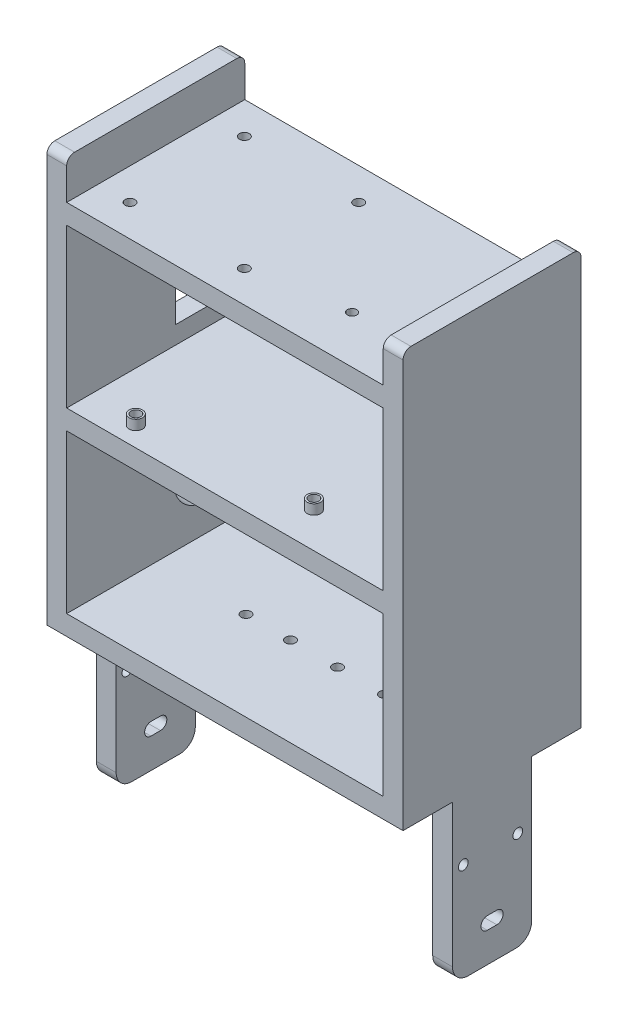
SolidWorks part; units mm, degrees
ref_plane "Front Plane" through (0, 0, 0) normal (0, 0, 1) x (1, 0, 0)
ref_plane "Top Plane" through (0, 0, 0) normal (0, 1, 0) x (1, 0, 0)
ref_plane "Right Plane" through (0, 0, 0) normal (1, 0, 0) x (0, 0, -1)
sketch "Sketch1" plane through (0, 0, 0) normal (0, 0, 1) x (1, 0, 0)
  line L0 (0, 0) -> (101.6, 0)
  line L1 (101.6, 0) -> (101.6, 127)
  line L2 (0, 0) -> (0, 127)
  line L3 (0, 57.15) -> (101.6, 57.15)
  line L4 (101.6, 57.15) -> (101.6, 50.8)
  line L5 (101.6, 50.8) -> (0, 50.8)
  line L6 (0, 50.8) -> (0, 57.15)
  line L7 (0, 114.3) -> (101.6, 114.3)
  line L8 (101.6, 114.3) -> (101.6, 107.95)
  line L9 (101.6, 107.95) -> (0, 107.95)
  line L10 (0, 107.95) -> (0, 114.3)
  line L11 (-6.35, 0) -> (-6.35, -6.35)
  line L12 (0, -6.35) -> (101.6, -6.35)
  line L13 (107.95, 0) -> (107.95, -6.35)
  line L14 (101.6, 127) -> (107.95, 127)
  line L15 (107.95, 127) -> (107.95, 0)
  line L16 (107.95, 0) -> (101.6, 0)
  line L17 (0, 127) -> (-6.35, 127)
  line L18 (-6.35, 127) -> (-6.35, 0)
  line L19 (-6.35, 0) -> (0, 0)
  line L20 (-6.35, -6.35) -> (0, -6.35)
  line L21 (107.95, -6.35) -> (101.6, -6.35)
  dimension "D1" = 101.6
  dimension "D2" = 127
  dimension "D3" = 57.15
  dimension "D4" = 6.35
  dimension "D5" = 114.3
  dimension "D6" = 6.35
  dimension "D7" = 6.35
  dimension "D8" = 6.35
  dimension "D9" = 6.35
extrude "Boss-Extrude1" add sketch "Sketch1" against normal blind 57.15 contours L16 L15 L14 L1 | L18 L19 L2 L17 | L9 L1 L7 L2 | L5 L1 L3 L2 | L21 L13 L16 L0 L19 L11 L20 L12 region at (-3.175, 63.5, 0) region at (50.8, -3.175, 0) region at (104.775, 63.5, 0) region at (50.8, 53.975, 0) region at (50.8, 111.125, 0)
sketch "Sketch2" plane through (107.95, 0, 0) normal (1, 0, 0) x (0, 0, -1)
  line L0 (28.575, -6.35) -> (28.575, 127) construction
  line L1 (57.15, -6.35) -> (0, -6.35) construction
  line L2 (57.15, 127) -> (0, 127) construction
  line L3 (41.275, -6.35) -> (41.275, -57.15)
  line L4 (15.875, -6.35) -> (15.875, -57.15)
  line L5 (15.875, -6.35) -> (41.275, -6.35)
  line L6 (15.875, -57.15) -> (41.275, -57.15)
  dimension "D1" = 12.7
  dimension "D2" = 50.8
extrude "Boss-Extrude2" add sketch "Sketch2" against normal blind 6.35
ref_plane "Plane1" through (50.8, 0, 0) normal (1, 0, 0) x (0, 0, -1)
mirror "Mirror1" about plane through (50.8, 0, 0) normal (1, 0, 0) of "Boss-Extrude2"
sketch "Sketch4" plane through (-6.35, 0, 0) normal (-1, 0, 0) x (0, 0, 1)
  line L0 (-30.1047, 127) -> (-28.575, -55.7505) construction
  line L1 (-57.15, 127) -> (0, 127) construction
  text T0 "<r90>LEEK</r></r>" font "Arial" height in points 36
extrude "Boss-Extrude3" add sketch "Sketch4" along normal blind 0.508
sketch "Sketch5" plane through (107.95, 0, 0) normal (1, 0, 0) x (0, 0, -1)
  line L0 (28.575, -55.7505) -> (28.575, -5.8921) construction
  line L1 (27.051, -45.527) -> (30.099, -45.527) construction
  line L2 (27.051, -43.495) -> (30.099, -43.495)
  line L3 (27.051, -47.559) -> (30.099, -47.559)
  line L5 (15.875, -57.15) -> (41.275, -57.15) construction
  arc A1 (27.051, -43.495) -> (27.051, -47.559) centre (27.051, -45.527) ccw
  arc A2 (30.099, -47.559) -> (30.099, -43.495) centre (30.099, -45.527) ccw
  point P8 (28.575, -45.527)
  dimension "D3" = 9.591
  dimension "D1" = 1.524
  dimension "D2" = 4.064
extrude "Cut-Extrude1" cut sketch "Sketch5" against normal through all
sketch "Sketch7" plane through (-6.35, 0, 0) normal (-1, 0, 0) x (0, 0, 1)
  circle A0 centre (-36.8351, -25.527) radius 1.5748
  circle A1 centre (-19.3345, -25.527) radius 1.5748
  arc A2 (-30.099, -43.495) -> (-30.099, -47.559) centre (-30.099, -45.527) ccw construction
  point P12 (-32.131, -45.527)
  dimension "D1" = 3.1496
  dimension "D2" = 17.5006
  dimension "D3" = 6.7361
  dimension "D4" = 20
fillet "Fillet1" radius 5.0013 4 edges at (-3.175, -57.15, -15.875) (-3.175, -57.15, -41.275) (104.775, -57.15, -41.275) (104.775, -57.15, -15.875)
extrude "Cut-Extrude2" cut sketch "Sketch7" against normal through all
sketch "Sketch8" plane through (-6.35, 0, 0) normal (-1, 0, 0) x (0, 0, 1)
  line L0 (-57.15, 127) -> (-57.15, -6.35) construction
  line L1 (-56.007, 21.2712) -> (-32.893, 21.2712)
  line L2 (-32.893, 21.2712) -> (-32.893, 16.8288)
  line L3 (-32.893, 16.8288) -> (-56.007, 16.8288)
  line L4 (-56.007, 16.8288) -> (-56.007, 21.2712)
  line L5 (-56.007, 19.05) -> (-32.893, 19.05) construction
  line L6 (-44.45, 30.607) -> (-44.45, 7.493) construction
  line L7 (-57.15, -6.35) -> (-41.275, -6.35) construction
  circle A0 centre (-44.45, 19.05) radius 10.033
  circle A1 centre (-44.45, 19.05) radius 11.557
  dimension "D1" = 12.7
  dimension "D2" = 20.066
  dimension "D3" = 23.114
  dimension "D6" = 25.4
  dimension "D4" = 23.114
  dimension "D5" = 4.4425
extrude "Cut-Extrude3" cut sketch "Sketch8" against normal up to surface (6.35 mm away) contours L1 A0 | L1 A0 L3 | L3 A0 region at (-6.35, 24.5313, -44.45) region at (-6.35, 19.05, -44.45) region at (-6.35, 13.5687, -44.45) up to face at (0, 25.4, -28.575)
extrude "Boss-Extrude6" add sketch "Sketch8<3>" along normal blind 3.81 contours L1 A1 A0 | L3 A1 A0 region at (-6.35, 30.3617, -44.45) region at (-6.35, 16.5835, -55.0128)
sketch "Sketch8<3>" plane through (-6.35, 0, 0) normal (-1, 0, 0) x (0, 0, 1) same geometry as "Sketch8"
sketch "Sketch10" plane through (0, 57.15, 0) normal (0, 1, 0) x (1, 0, 0)
  line L0 (0, 57.15) -> (0, 0) construction
  line L1 (0, 0) -> (101.6, 0) construction
  circle A0 centre (15.875, 6.317) radius 1.5875
  circle A1 centre (17.145, 54.577) radius 1.5875
  circle A2 centre (67.945, 11.397) radius 1.5875
  circle A3 centre (67.945, 39.337) radius 1.5875
  circle A4 centre (15.875, 6.317) radius 2.159
  circle A5 centre (17.145, 54.577) radius 2.159
  circle A6 centre (67.945, 39.337) radius 2.159
  circle A7 centre (67.945, 11.397) radius 2.159
  dimension "D1" = 15.875
  dimension "D2" = 3.175
  dimension "D4" = 48.26
  dimension "D6" = 52.07
  dimension "D8" = 27.94
  dimension "D9" = 4.318
  dimension "D3" = 6.317
  dimension "D5" = 1.27
  dimension "D7" = 5.08
extrude "Cut-Extrude5" cut sketch "Sketch10" against normal up to surface (6.35 mm away) contours A0 | A2 | A3 | A1 region at (15.875, 57.15, -6.317) up to face at (50.8, 50.8, -28.575)
sketch "Sketch11" plane through (0, 114.3, 0) normal (0, 1, 0) x (1, 0, 0)
  line L0 (0, 0) -> (101.6, 0) construction
  line L1 (0, 57.15) -> (0, 0) construction
  circle A0 centre (10.16, 10.16) radius 1.5875
  circle A1 centre (46.8605, 10.16) radius 1.5875
  circle A2 centre (46.8605, 46.8605) radius 1.5875
  circle A3 centre (10.16, 46.8605) radius 1.5875
  dimension "D1" = 3.175
  dimension "D4" = 36.7005
  dimension "D5" = 36.7005
  dimension "D2" = 10.16
  dimension "D3" = 10.16
extrude "Cut-Extrude6" cut sketch "Sketch11" against normal up to surface (6.35 mm away) up to face at (50.8, 107.95, -28.575)
sketch "Sketch12" plane through (0, 114.3, 0) normal (0, 1, 0) x (1, 0, 0)
  line L0 (0, 0) -> (101.6, 0) construction
  line L1 (101.6, 57.15) -> (101.6, 0) construction
  circle A0 centre (91.3456, 15.24) radius 1.4999
  circle A1 centre (76.3444, 15.24) radius 1.4999
  dimension "D1" = 2.9997
  dimension "D4" = 15.0012
  dimension "D2" = 15.24
  dimension "D3" = 10.2544
extrude "Cut-Extrude7" cut sketch "Sketch12" against normal up to surface (6.35 mm away) up to face at (10.16, 107.95, -45.273)
sketch "Sketch13" plane through (0, 0, 0) normal (0, 1, 0) x (1, 0, 0)
  line L0 (50.8, 57.15) -> (50.8, 0) construction
  line L1 (0, 57.15) -> (101.6, 57.15) construction
  line L2 (0, 0) -> (101.6, 0) construction
  line L3 (0, 28.575) -> (101.6, 28.575) construction
  line L4 (0, 57.15) -> (0, 0) construction
  line L5 (101.6, 57.15) -> (101.6, 0) construction
  circle A4 centre (58.3438, 28.575) radius 1.5875
  circle A5 centre (43.2562, 28.575) radius 1.5875
  circle A6 centre (73.4314, 28.575) radius 1.5875
  circle A7 centre (28.9814, 28.575) radius 1.5875
  dimension "D5" = 3.175
  dimension "D6" = 15.0876
  dimension "D7" = 44.45
  dimension "D8" = 15.0876
extrude "Cut-Extrude8" cut sketch "Sketch13" against normal up to surface (6.35 mm away) up to face at (50.8, -6.35, -28.575)
sketch "Sketch9" plane through (-6.35, 0, 0) normal (-1, 0, 0) x (0, 0, 1)
  line L0 (-47.5894, 62.865) -> (-34.8894, 62.865)
  line L1 (-57.15, -6.35) -> (-41.275, -6.35) construction
  line L2 (-47.5894, 62.865) -> (-47.5894, 73.787)
  line L3 (-47.5894, 73.787) -> (-34.8894, 73.787)
  line L4 (-34.8894, 73.787) -> (-34.8894, 62.865)
  line L5 (-57.15, 127) -> (-57.15, -6.35) construction
  dimension "D1" = 69.215
  dimension "D2" = 12.7
  dimension "D3" = 10.922
  dimension "D4" = 9.5606
extrude "Cut-Extrude4" cut sketch "Sketch9" against normal up to surface (6.35 mm away) up to face at (0, 82.55, -28.575)
extrude "Boss-Extrude9" add sketch "Sketch10<5>" along normal blind 3.175 separate body contours A4 A0 | A7 A2 | A6 A3 | A5 A1 region at (13.7771, 57.15, -6.317) region at (15.0471, 57.15, -54.577) region at (65.8471, 57.15, -39.337) region at (65.8471, 57.15, -11.397)
sketch "Sketch10<5>" plane through (0, 57.15, 0) normal (0, 1, 0) x (1, 0, 0) same geometry as "Sketch10"
fillet "Fillet2" radius 2.54 4 edges at (104.775, 127, -57.15) (-3.175, 127, -57.15) (104.775, 127, 0) (-3.175, 127, 0)
